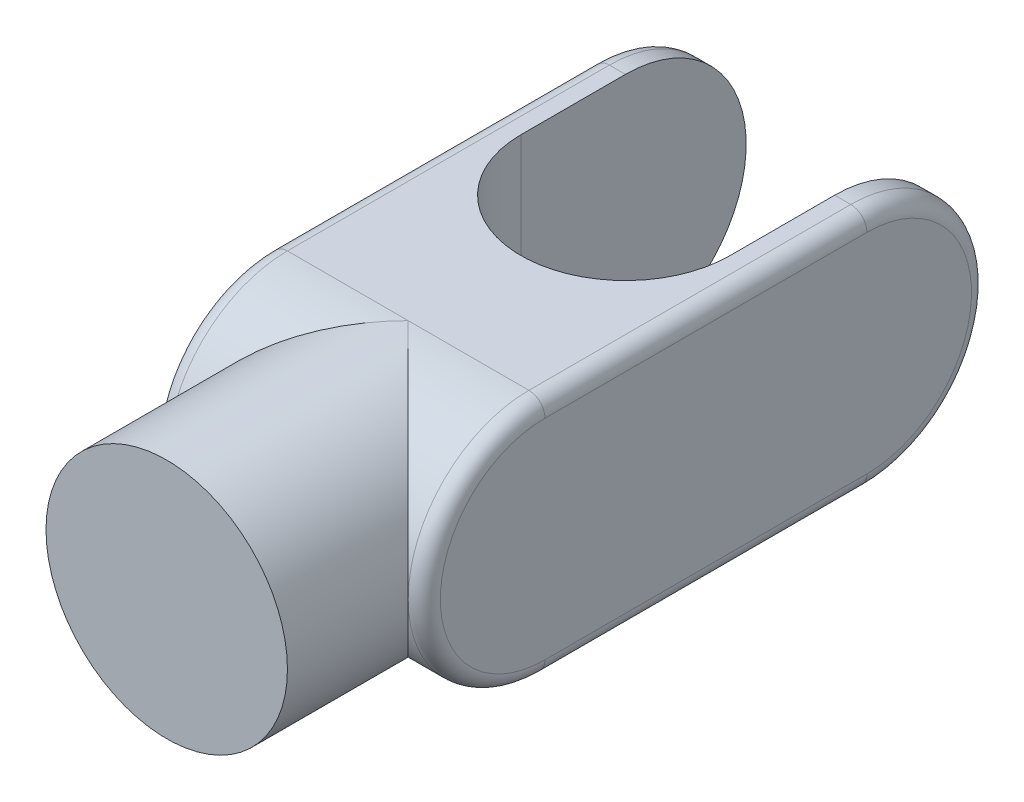
SolidWorks part; units mm, degrees
ref_plane "前视基准面" through (0, 0, 0) normal (0, 0, 1) x (1, 0, 0)
ref_plane "上视基准面" through (0, 0, 0) normal (0, 1, 0) x (1, 0, 0)
ref_plane "右视基准面" through (0, 0, 0) normal (1, 0, 0) x (0, 0, -1)
sketch "草图1" plane through (0, 0, 0) normal (0, 0, 1) x (1, 0, 0)
  circle A0 centre (0, 0) radius 150
extrude "凸台-拉伸1" add sketch "草图1" along normal mid plane 300
sketch "草图3" plane through (0, 0, 0) normal (1, 0, 0) x (0, 0, -1)
  line L0 (150, -150) -> (150, 150) construction
  line L1 (150, 150) -> (550, 150)
  line L3 (550, -150) -> (150, -150)
  arc A0 (150, 150) -> (150, -150) centre (150, 0) ccw
  arc A1 (550, -150) -> (550, 150) centre (550, 0) ccw
  dimension "D1" = 400
extrude "凸台-拉伸2" add sketch "草图3" along normal mid plane 340 contours L1 A1 L3 A0
fillet "圆角1" radius 20 4 edges at (170, 0, 0) (170, -150, -350) (170, 0, -700) (170, 150, -350)
fillet "圆角2" radius 20 4 edges at (-170, 0, 0) (-170, -150, -350) (-170, 0, -700) (-170, 150, -350)
sketch "草图4" plane through (0, 0, 0) normal (0, 1, 0) x (1, 0, 0)
  line L5 (-130, 420) -> (-130, 938.5306)
  line L6 (-130, 938.5306) -> (130, 938.5306)
  line L7 (130, 938.5306) -> (130, 420)
  arc A3 (-130, 420) -> (130, 420) centre (0, 420) ccw
extrude "切除-拉伸1" cut sketch "草图4" against normal mid plane 340
